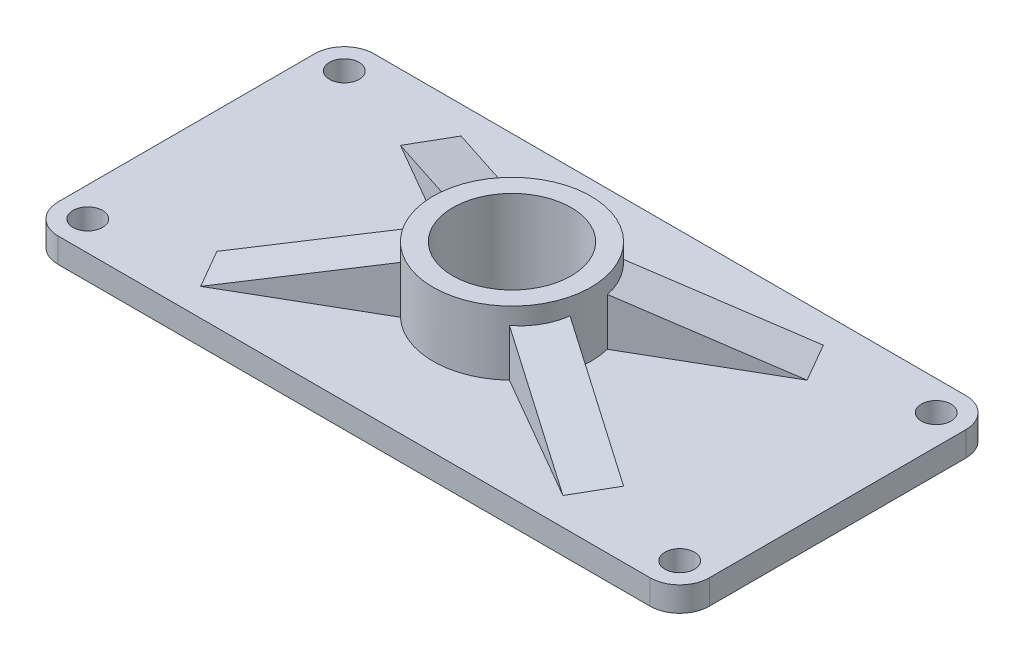
SolidWorks part; units mm, degrees
material "Thornel Mat VMA"
ref_plane "Front Plane" through (0, 0, 0) normal (0, 0, 1) x (1, 0, 0)
ref_plane "Top Plane" through (0, 0, 0) normal (0, 1, 0) x (1, 0, 0)
ref_plane "Right Plane" through (0, 0, 0) normal (1, 0, 0) x (0, 0, -1)
sketch "Sketch1" plane through (0, 0, 0) normal (0, 1, 0) x (1, 0, 0)
  line L1 (60, -32) -> (-60, -32)
  line L2 (66, -26) -> (66, 26)
  line L3 (60, 32) -> (-60, 32)
  line L4 (-66, -26) -> (-66, 26)
  line L5 (66, -32) -> (-66, 32) construction
  line L6 (66, 32) -> (-66, -32) construction
  arc A0 (66, 26) -> (60, 32) centre (60, 26) ccw
  arc A1 (60, -32) -> (66, -26) centre (60, -26) ccw
  arc A2 (-60, -32) -> (-66, -26) centre (-60, -26) cw
  arc A3 (-60, 32) -> (-66, 26) centre (-60, 26) ccw
  circle A8 centre (0, 0) radius 12
  circle A9 centre (0, 0) radius 16
  circle A10 centre (60, -26) radius 3
  circle A11 centre (-60, -26) radius 3
  circle A12 centre (-60, 26) radius 3
  circle A13 centre (60, 26) radius 3
  point P0 (0, 0)
  dimension "D3" = 6
  dimension "D4" = 24
  dimension "D5" = 32
  dimension "D6" = 6
  dimension "D1" = 132
  dimension "D2" = 64
extrude "Boss-Extrude1" add sketch "Sketch1" along normal blind 5 contours L3 A3 L4 A2 L1 A1 L2 A0 A9 region at (0, 0, 30.533)
extrude "Boss-Extrude2" add sketch "Sketch1<3>" along normal blind 18 contours A9 A8 region at (-15.5475, 0, 0)
sketch "Sketch1<3>" plane through (0, 0, 0) normal (0, 1, 0) x (1, 0, 0) same geometry as "Sketch1"
sketch "Sketch2" plane through (0, 5, 0) normal (0, 1, 0) x (1, 0, 0)
  line L0 (0, 0) -> (-66, 38.1051) construction
  line L1 (-66, 38.1051) -> (-66, 0) construction
  line L2 (-66, 0) -> (0, 0) construction
  line L3 (-66, -26) -> (-66, 26) construction
  dimension "D1" = 30
ref_plane "Plane1" through (0, 0, 0) normal (0.5, 0, -0.866) x (-0.866, 0, -0.5)
sketch "Sketch3" plane through (0, 0, 0) normal (0.5, 0, -0.866) x (-0.866, 0, -0.5)
  line L0 (12, 15.7223) -> (45, 5)
  line L1 (45, 5) -> (12, 5)
  line L2 (12, 5) -> (12, 15.7223)
  line L3 (0, 0) -> (0, 25.4043) construction
  line L4 (-35.9615, 5) -> (-41.9615, 5) construction
  line L7 (-45, 5) -> (-12, 5)
  line L8 (-12, 15.7223) -> (-45, 5)
  line L9 (-12, 5) -> (-12, 15.7223)
  dimension "D1" = 18
  dimension "D2" = 45
  dimension "D3" = 12
extrude "Boss-Extrude3" add sketch "Sketch3" along normal mid plane 9
mirror "Mirror1" about plane through (0, 0, 0) normal (0, 0, 1) of "Boss-Extrude3"
